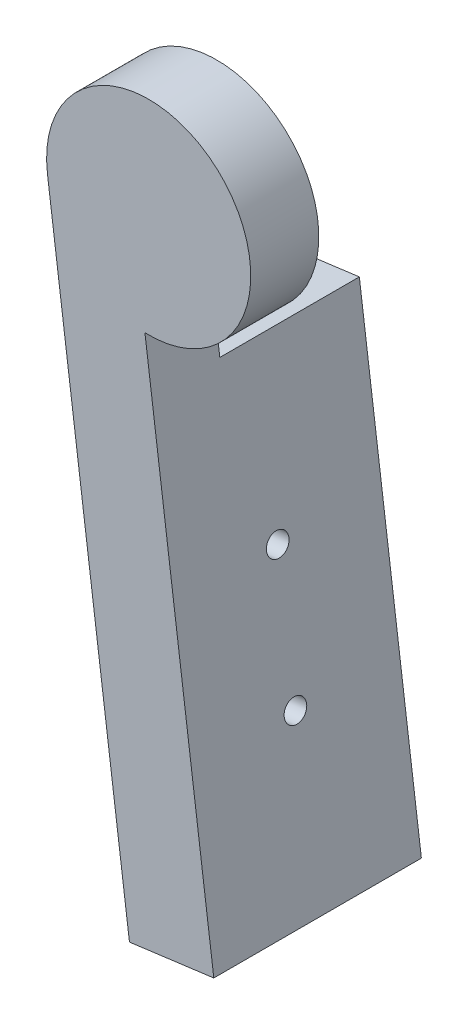
SolidWorks part; units mm, degrees
ref_plane "Front Plane" through (0, 0, 0) normal (0, 0, 1) x (1, 0, 0)
ref_plane "Top Plane" through (0, 0, 0) normal (0, 1, 0) x (1, 0, 0)
ref_plane "Right Plane" through (0, 0, 0) normal (1, 0, 0) x (0, 0, -1)
sketch "Sketch1" plane through (0, 0, 0) normal (0, 0, 1) x (1, 0, 0)
  circle A0 centre (0, 0) radius 19.05
  dimension "D1" = 38.1
extrude "Boss-Extrude1" add sketch "Sketch1" along normal blind 12.7
sketch "Sketch2" plane through (0, 0, 12.7) normal (0, 0, 1) x (1, 0, 0)
  line L0 (-18.8877, -2.4811) -> (-3.5875, -118.9555)
  line L1 (-3.5875, -118.9555) -> (12.1523, -116.8879)
  line L2 (12.1523, -116.8879) -> (-0.7015, -19.0371)
  line L3 (12.1523, -116.8879) -> (0.5737, -28.7451) construction
  circle A0 centre (0, 0) radius 19.05 construction
  arc A1 (-18.8877, -2.4811) -> (-0.7015, -19.0371) centre (0, 0) ccw
extrude "Boss-Extrude2" add sketch "Sketch2" against normal up to surface (12.7 mm away) up to face at (19.05, 0, 0)
sketch "Sketch3" plane through (0, 0, 0) normal (0, 0, -1) x (-1, 0, 0)
  line L0 (3.5875, -118.9555) -> (-12.1523, -116.8879)
  line L1 (3.5875, -118.9555) -> (15.1661, -30.8127)
  line L2 (-12.1523, -116.8879) -> (-0.5737, -28.7451)
  line L3 (15.1661, -30.8127) -> (-0.5737, -28.7451)
  line L4 (-0.5737, -28.7451) -> (15.1661, -30.8127) construction
extrude "Boss-Extrude3" add sketch "Sketch3" along normal blind 26.035
sketch "Sketch4" plane through (-18.8877, -2.4811, 0) normal (-0.9915, -0.1302, 0) x (0, 0, 1)
  line L0 (-6.6675, -173.9903) -> (-6.6675, 75.1409) construction
  line L1 (12.7, 0) -> (12.7, -117.475) construction
  line L2 (-26.035, -117.475) -> (-26.035, -28.575) construction
  line L3 (-203.6191, -60.325) -> (5.4685, -60.325) construction
  line L4 (-203.6191, -85.725) -> (10.4297, -85.725) construction
  circle A0 centre (-6.6675, -60.325) radius 2.0955
  circle A1 centre (-6.6675, -85.725) radius 2.0955
  dimension "D1" = 4.191
extrude "Cut-Extrude1" cut sketch "Sketch4" against normal through all
